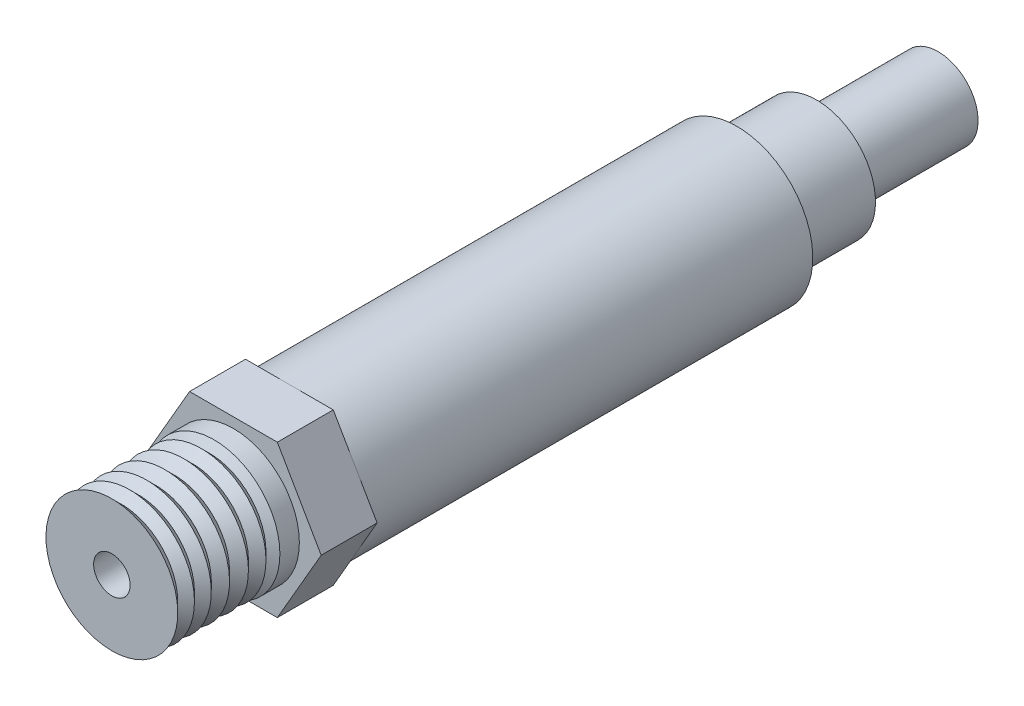
SolidWorks part; units mm, degrees
material "Chrome Stainless Steel"
ref_plane "Front Plane" through (0, 0, 0) normal (0, 0, 1) x (1, 0, 0)
ref_plane "Top Plane" through (0, 0, 0) normal (0, 1, 0) x (1, 0, 0)
ref_plane "Right Plane" through (0, 0, 0) normal (1, 0, 0) x (0, 0, -1)
sketch "Sketch1" plane through (0, 0, 0) normal (0, 0, 1) x (1, 0, 0)
  circle A0 centre (0, 0) radius 6.8834
extrude "Extrude1" add sketch "Sketch1" along normal blind 10.668
sketch "Sketch2" plane through (0, 0, 0) normal (1, 0, 0) x (0, 0, -1)
  line L0 (-10.668, 6.8834) -> (-9.6729, 5.8883)
  line L1 (-9.6729, 5.8883) -> (-8.8024, 6.7589)
  line L2 (-8.8024, 6.7589) -> (-7.9219, 5.8785)
  line L3 (-7.9219, 5.8785) -> (-7.0415, 6.7589)
  line L4 (-7.0415, 6.7589) -> (-6.0899, 5.8073)
  line L5 (-6.0899, 5.8073) -> (-5.1383, 6.7589)
  line L7 (-5.1383, 6.7589) -> (-4.1512, 5.7717)
  line L8 (-4.1512, 5.7717) -> (-3.164, 6.7589)
  line L9 (-3.164, 6.7589) -> (-2.248, 5.8429)
  line L10 (-2.248, 5.8429) -> (-1.332, 6.7589)
  line L11 (-1.332, 6.7589) -> (-0.5147, 5.9416)
  line L12 (-0.5147, 5.9416) -> (0, 6.8834)
  line L13 (-10.668, 6.8834) -> (0, 6.8834)
  line L17 (-12.004, 0) -> (1.336, 0) construction
revolve "Cut-Revolve5" cut sketch "Sketch2" angle 360 about L17
extrude "Extrude2" add sketch "Sketch1<2>" against normal blind 2.032
sketch "Sketch1<2>" plane through (0, 0, 0) normal (0, 0, 1) x (1, 0, 0) same geometry as "Sketch1"
sketch "Sketch3" plane through (0, 0, 10.668) normal (0, 0, 1) x (1, 0, 0)
  circle A0 centre (0, 0) radius 1.905
extrude "Cut-Extrude1" cut sketch "Sketch3" against normal blind 6.35
sketch "Sketch4" plane through (0, 0, -2.032) normal (0, 0, -1) x (-1, 0, 0)
  line L0 (-4.5827, 7.9375) -> (4.5827, 7.9375)
  line L1 (-4.5827, -7.9375) -> (4.5827, -7.9375)
  line L2 (-4.5827, -7.9375) -> (-9.1654, 0)
  line L3 (-9.1654, 0) -> (-4.5827, 7.9375)
  line L4 (4.5827, 7.9375) -> (9.1654, 0)
  line L5 (9.1654, 0) -> (4.5827, -7.9375)
  dimension "D1" = 7.9375
  dimension "D2" = 7.9375
  dimension "D3" = 7.9375
  dimension "D4" = 7.9375
  dimension "D5" = 7.9375
extrude "Extrude3" add sketch "Sketch4" along normal blind 5.842
sketch "Sketch5" plane through (0, 0, -7.874) normal (0, 0, -1) x (-1, 0, 0)
  circle A0 centre (0, 0) radius 7.9375
extrude "Extrude4" add sketch "Sketch5" along normal blind 46.736
sketch "Sketch6" plane through (0, 0, -54.61) normal (0, 0, -1) x (-1, 0, 0)
  circle A0 centre (0, 0) radius 6.1516
extrude "Extrude5" add sketch "Sketch6" along normal blind 8.3344
sketch "Sketch7" plane through (0, 0, -62.9444) normal (0, 0, -1) x (-1, 0, 0)
  circle A0 centre (0, 0) radius 4.1672
extrude "Extrude6" add sketch "Sketch7" along normal blind 12.7
